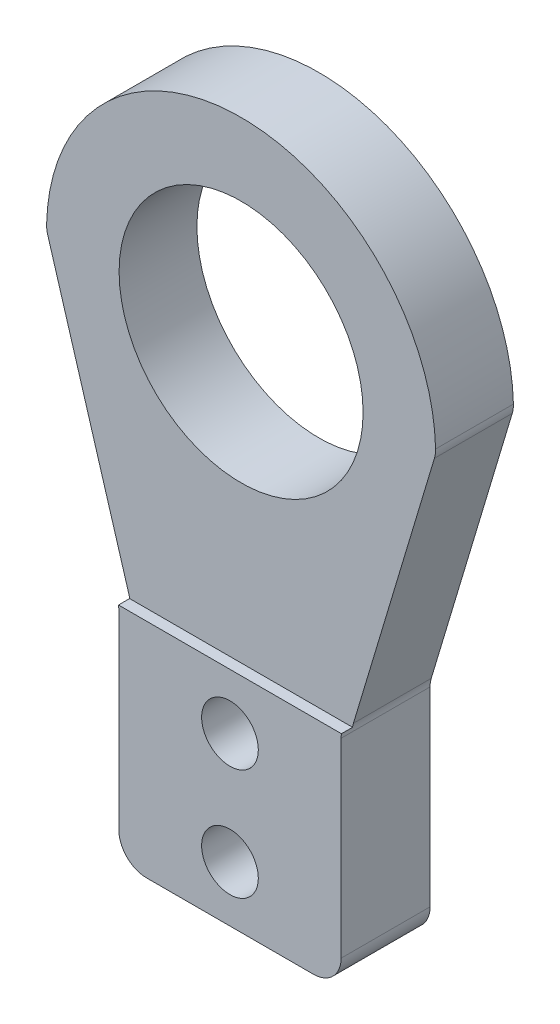
SolidWorks part; units mm, degrees
ref_plane "Front Plane" through (0, 0, 0) normal (0, 0, 1) x (1, 0, 0)
ref_plane "Top Plane" through (0, 0, 0) normal (0, 1, 0) x (1, 0, 0)
ref_plane "Right Plane" through (0, 0, 0) normal (1, 0, 0) x (0, 0, -1)
sketch "Sketch1" plane through (0, 0, 0) normal (0, 0, 1) x (1, 0, 0)
  line L0 (0, -353.8104) -> (0, 17336.7087) construction
  line L1 (-10, -15) -> (-10, 5)
  line L2 (-10, 5) -> (-17.5, 30)
  line L3 (10, -15) -> (-10, -15)
  line L4 (10, -15) -> (10, 5)
  line L5 (10, 5) -> (17.5, 30)
  arc A0 (17.5, 30) -> (-17.5, 30) centre (0, 30) ccw
  circle A1 centre (0, 0) radius 2.55
  circle A2 centre (0, -10) radius 2.55
  dimension "D1" = 5.1
  dimension "D2" = 5.1
  dimension "D3" = 10
  dimension "D4" = 35
  dimension "D5" = 30
  dimension "D7" = 20
  dimension "D6" = 5
  dimension "D8" = 20
  dimension "D9" = 10
  dimension "D10" = 20
extrude "Boss-Extrude2" add sketch "Sketch1" along normal blind 8
fillet "Fillet1" radius 2.5 6 edges at (-17.5, 30, 4) (17.5, 30, 4) (10, 5, 4) (10, -15, 4) (-10, -15, 4) (-10, 5, 4)
sketch "Sketch3" plane through (0, 0, 8) normal (0, 0, 1) x (1, 0, 0)
  circle A0 centre (0, 30) radius 10.975
  dimension "D1" = 21.95
extrude "Cut-Extrude2" cut sketch "Sketch3" against normal through all
sketch "Sketch6" plane through (0, 0, 8) normal (0, 0, 1) x (1, 0, 0)
  line L0 (-7.5, -15) -> (7.5, -15) construction
  line L1 (-20, 5) -> (20, 5)
  line L2 (-20, 5) -> (-20, 55)
  line L3 (-20, 55) -> (20, 55)
  line L4 (20, 5) -> (20, 55)
  line L5 (-20, 5) -> (20, 55) construction
  line L6 (-20, 55) -> (20, 5) construction
  point P0 (0, 30)
  dimension "D1" = 20
  dimension "D2" = 40
extrude "Cut-Extrude5" cut sketch "Sketch6" against normal blind 1
